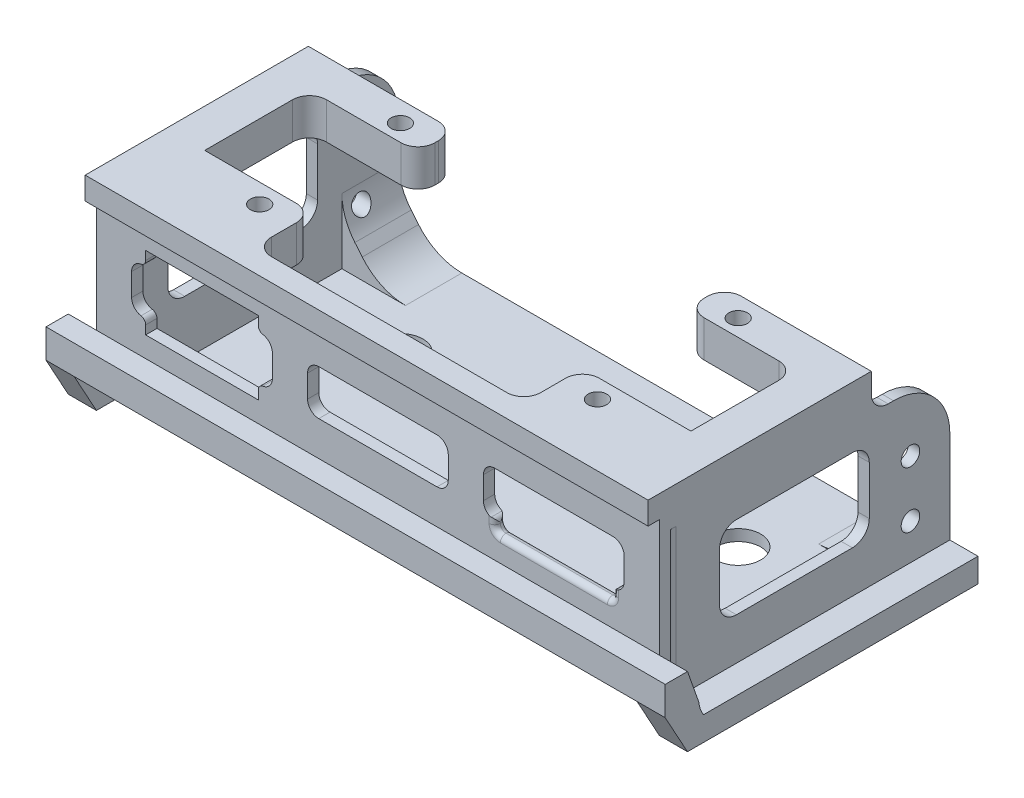
SolidWorks part; units mm, degrees
ref_plane "前视基准面" through (0, 0, 0) normal (0, 0, 1) x (1, 0, 0)
ref_plane "上视基准面" through (0, 0, 0) normal (0, 1, 0) x (1, 0, 0)
ref_plane "右视基准面" through (0, 0, 0) normal (1, 0, 0) x (0, 0, -1)
sketch "草图1" plane through (0, 0, 0) normal (0, 0, 1) x (1, 0, 0)
  line L1 (0, 0) -> (100, 0)
  line L2 (0, 0) -> (0, 30)
  line L3 (0, 30) -> (100, 30)
  line L4 (100, 0) -> (100, 30)
  dimension "D1" = 100
  dimension "D2" = 30
extrude "凸台-拉伸1" add sketch "草图1" along normal blind 2
sketch "草图2" plane through (0, 0, 2) normal (0, 0, 1) x (1, 0, 0)
  line L0 (0, 26) -> (100.6534, 26)
  line L4 (0, 30) -> (0, 0)
  line L5 (0, 0) -> (100, 0)
  line L6 (100, 0) -> (100, 30)
  line L7 (100, 30) -> (0, 30)
  line L8 (0, 30) -> (0, 0)
  line L9 (0, 0) -> (100, 0)
  line L10 (100, 0) -> (100, 30)
  line L11 (100, 30) -> (0, 30)
  line M6 (0, 30) -> (0, 0)
  line M8 (100, 0) -> (100, 30)
  line M9 (100, 30) -> (0, 30)
  dimension "D2" = 4
  dimension "D1" = 0
extrude "凸台-拉伸2" add sketch "草图2" along normal blind 2 contours L0 M6 M8 M9
sketch "草图3" plane through (0, 0, 2) normal (0, 0, 1) x (1, 0, 0)
  line L0 (37.5, 17.2904) -> (37.5, 13.2904)
  line L1 (8.25, 19.2904) -> (29.25, 19.2904)
  line L2 (6.25, 17.2904) -> (6.25, 13.2904)
  line L3 (8.25, 11.2904) -> (29.25, 11.2904)
  line L4 (100, 26) -> (0, 26)
  line L5 (0, 26) -> (0, 0)
  line L6 (0, 0) -> (100, 0)
  line L7 (100, 0) -> (100, 26)
  line L8 (100, 26) -> (0, 26)
  line L9 (0, 26) -> (0, 0)
  line L10 (0, 0) -> (100, 0)
  line L11 (100, 0) -> (100, 26)
  line L12 (31.25, 17.2904) -> (31.25, 13.2904)
  line L13 (39.5, 19.2904) -> (60.5, 19.2904)
  line L14 (62.5, 17.2904) -> (62.5, 13.2904)
  line L15 (39.5, 11.2904) -> (60.5, 11.2904)
  line L16 (68.75, 17.2904) -> (68.75, 13.2904)
  line L17 (70.75, 19.2904) -> (91.75, 19.2904)
  line L18 (93.75, 17.2904) -> (93.75, 13.2904)
  line L19 (70.75, 11.2904) -> (91.75, 11.2904)
  arc A0 (29.25, 19.2904) -> (31.25, 17.2904) centre (29.25, 17.2904) cw
  arc A1 (31.25, 13.2904) -> (29.25, 11.2904) centre (29.25, 13.2904) cw
  arc A2 (6.25, 13.2904) -> (8.25, 11.2904) centre (8.25, 13.2904) ccw
  arc A3 (6.25, 17.2904) -> (8.25, 19.2904) centre (8.25, 17.2904) cw
  arc A4 (37.5, 17.2904) -> (39.5, 19.2904) centre (39.5, 17.2904) cw
  arc A5 (37.5, 13.2904) -> (39.5, 11.2904) centre (39.5, 13.2904) ccw
  arc A6 (60.5, 19.2904) -> (62.5, 17.2904) centre (60.5, 17.2904) cw
  arc A7 (62.5, 13.2904) -> (60.5, 11.2904) centre (60.5, 13.2904) cw
  arc A8 (68.75, 17.2904) -> (70.75, 19.2904) centre (70.75, 17.2904) cw
  arc A9 (68.75, 13.2904) -> (70.75, 11.2904) centre (70.75, 13.2904) ccw
  arc A10 (91.75, 19.2904) -> (93.75, 17.2904) centre (91.75, 17.2904) cw
  arc A11 (93.75, 13.2904) -> (91.75, 11.2904) centre (91.75, 13.2904) cw
  dimension "D2" = 2
  dimension "D3" = 8
  dimension "D4" = 25
  dimension "D5" = 6.25
  dimension "D1" = 0
  dimension "D6" = 3
extrude "切除-拉伸1" cut sketch "草图3" against normal blind 2 contours L2 A2 L3 A1 L12 A0 L1 A3 | L0 A5 L15 A7 L14 A6 L13 A4 | L16 A9 L19 A11 L18 A10 L17 A8
sketch "草图4" plane through (100, 0, 0) normal (1, 0, 0) x (0, 0, -1)
  line L1 (-2, 0) -> (-5.9583, 0)
  line L2 (-2, 0) -> (-2, 5.1375)
  line L3 (-2, 5.1375) -> (-5.9583, 5.1375)
  line L4 (-5.9583, 0) -> (-5.9583, 5.1375)
  line L5 (5.0712, -5.2066) -> (49.6052, -5.2066)
  line L6 (0, 0) -> (0, 30)
  line L7 (0, 30) -> (-4, 30)
  line L8 (-4, 30) -> (-4, 26)
  line L9 (-4, 26) -> (-2, 26)
  line L10 (-2, 26) -> (-2, 0)
  line L11 (-2, 0) -> (0, 0)
  line L12 (0, 0) -> (0, 30)
  line L13 (0, 30) -> (-4, 30)
  line L14 (-4, 30) -> (-4, 26)
  line L15 (-4, 26) -> (-2, 26)
  line L16 (-2, 26) -> (-2, 0)
  line L17 (-2, 0) -> (0, 0)
  line L18 (5.0712, -5.2066) -> (5.0712, -7.2061)
  line L19 (5.0712, -7.2061) -> (49.6052, -7.2061)
  line L20 (49.6052, -5.2066) -> (49.6052, -7.2061)
  arc A0 (0, 0) -> (5.0712, -5.2066) centre (5.0693, -0.1355) ccw
  arc A1 (-2, 0) -> (5.0712, -7.2061) centre (5.0693, -0.1355) ccw
  line M11 (-2, 26) -> (-2, 0)
  line M12 (-2, 0) -> (0, 0)
  dimension "D1" = 0
extrude "凸台-拉伸3" add sketch "草图4" against normal blind 100 contours L4 L1 L3 M11 | A1 L18 A0 M12 | L20 L5 L18 L19
sketch "草图5" plane through (100, 0, 0) normal (1, 0, 0) x (0, 0, -1)
  line L0 (-2, 5.1375) -> (0, 5.1375)
  line L1 (-5.9583, 0) -> (-2.0013, -7.2061)
  line L2 (-2.0013, -7.2061) -> (17.8074, -7.2061)
  line L3 (-2, 5.1375) -> (0.8406, -2.9345)
  line L4 (0.8406, -2.9345) -> (49.6052, -2.9345)
  line L5 (49.6052, -2.9345) -> (49.6052, -7.2061)
  line L11 (0, 0) -> (0, 30)
  line L12 (0, 30) -> (-4, 30)
  line L13 (-4, 30) -> (-4, 26)
  line L14 (-4, 26) -> (-2, 26)
  line L15 (-2, 26) -> (-2, 5.1375)
  line L16 (-2, 5.1375) -> (-5.9583, 5.1375)
  line L17 (-5.9583, 5.1375) -> (-5.9583, 0)
  line L18 (-5.9583, 0) -> (-2, 0)
  line L19 (5.0712, -7.2061) -> (49.6052, -7.2061)
  line L20 (49.6052, -7.2061) -> (49.6052, -5.2066)
  line L21 (49.6052, -5.2066) -> (5.0712, -5.2066)
  line L22 (0, 0) -> (0, 30)
  line L23 (0, 30) -> (-4, 30)
  line L24 (-4, 30) -> (-4, 26)
  line L25 (-4, 26) -> (-2, 26)
  line L26 (-2, 26) -> (-2, 5.1375)
  line L27 (-2, 5.1375) -> (-5.9583, 5.1375)
  line L28 (-5.9583, 5.1375) -> (-5.9583, 0)
  line L29 (-5.9583, 0) -> (-2, 0)
  line L30 (5.0712, -7.2061) -> (49.6052, -7.2061)
  line L31 (49.6052, -7.2061) -> (49.6052, -5.2066)
  line L32 (49.6052, -5.2066) -> (5.0712, -5.2066)
  arc A2 (-2, 0) -> (5.0712, -7.2061) centre (5.0693, -0.1355) ccw
  arc A3 (0, 0) -> (5.0712, -5.2066) centre (5.0693, -0.1355) ccw
  arc A4 (-2, 0) -> (5.0712, -7.2061) centre (5.0693, -0.1355) ccw
  arc A5 (0, 0) -> (5.0712, -5.2066) centre (5.0693, -0.1355) ccw
  line M19 (-2, 5.1375) -> (-5.9583, 5.1375)
  line M20 (-5.9583, 5.1375) -> (-5.9583, 0)
  line M21 (-5.9583, 0) -> (-2, 0)
  arc M22 (-2, 0) -> (5.0712, -7.2061) centre (5.0693, -0.1355) ccw
  line M23 (5.0712, -7.2061) -> (49.6052, -7.2061)
  line M24 (49.6052, -7.2061) -> (49.6052, -5.2066)
  line M25 (49.6052, -5.2066) -> (5.0712, -5.2066)
  arc M26 (5.0712, -5.2066) -> (0, 0) centre (5.0693, -0.1355) cw
  dimension "D1" = 0
extrude "凸台-拉伸4" add sketch "草图5" along normal blind 5 contours L3 M19 M20 M21 M22 M23 M24 M25 M26 | L1 L2 M22 M21 | L5 L4 M26 M25
sketch "草图6" plane through (100, 0, 0) normal (1, 0, 0) x (0, 0, -1)
  line L0 (5.0712, -5.2066) -> (49.6052, -5.2066) construction
  line L1 (5.0712, -5.2066) -> (49.6052, -5.2066)
  line L3 (0, 23.4873) -> (49.6052, 23.4873)
  line L4 (0, 23.4873) -> (0, -5.2066)
  line L5 (0, -5.2066) -> (49.6052, -5.2066)
  line L6 (-2, 26) -> (-2, 5.1375)
  line L7 (-2, 5.1375) -> (0.0197, -0.6016)
  line L8 (0, 0) -> (0, 30)
  line L9 (0, 30) -> (-4, 30)
  line L10 (-4, 30) -> (-4, 26)
  line L11 (-4, 26) -> (-2, 26)
  line L12 (-2, 26) -> (-2, 5.1375)
  line L13 (-2, 5.1375) -> (0.0197, -0.6016)
  line L14 (0, 0) -> (0, 30)
  line L15 (0, 30) -> (-4, 30)
  line L16 (-4, 30) -> (-4, 26)
  line L17 (-4, 26) -> (-2, 26)
  line L18 (49.6052, 23.4873) -> (49.6052, -5.2066)
  arc A0 (0.8406, -2.9345) -> (5.0712, -5.2066) centre (5.0693, -0.1355) ccw construction
  arc A1 (0, 0) -> (0.0197, -0.6016) centre (5.0693, -0.1355) ccw
  arc A2 (0, 0) -> (0.0197, -0.6016) centre (5.0693, -0.1355) ccw
  arc A3 (0.8406, -2.9345) -> (5.0712, -5.2066) centre (5.0693, -0.1355) ccw
  arc A4 (0.0197, -0.6016) -> (0.8406, -2.9345) centre (5.0693, -0.1355) ccw construction
  arc A5 (0.0197, -0.6016) -> (0.8406, -2.9345) centre (5.0693, -0.1355) ccw
  arc M14 (0.0197, -0.6016) -> (0, 0) centre (5.0693, -0.1355) cw
  line M15 (0, 0) -> (0, 30)
  dimension "D1" = 0
extrude "凸台-拉伸5" add sketch "草图6" against normal blind 2 contours A5 A3 L1 L18 L3 L4 M14 M15
fillet "圆角1" radius 3 1 edges at (100, 15.5687, 2)
sketch "草图7" plane through (0, 30, 0) normal (0, 1, 0) x (1, 0, 0)
  line L0 (50, 0) -> (50, 26.3995) construction
  line L1 (100, 1) -> (100, 49.6052) construction
  line L2 (73.9207, 0) -> (100, 0)
  line L3 (73.9207, 0) -> (73.9207, 10.4199)
  line L4 (100, 0) -> (0, 0)
  line L5 (0, 0) -> (0, -4)
  line L6 (0, -4) -> (100, -4)
  line L7 (100, -4) -> (100, 0)
  line L8 (100, 0) -> (0, 0)
  line L9 (0, 0) -> (0, -4)
  line L10 (0, -4) -> (100, -4)
  line L11 (100, -4) -> (100, 0)
  line L12 (73.9207, 10.4199) -> (100, 10.4199)
  line L13 (100, 0) -> (100, 10.4199)
  line L14 (100, 1) -> (100, 49.6052)
  line L16 (73.9207, 29.0335) -> (100, 29.0335)
  line L17 (73.9207, 29.0335) -> (73.9207, 35.6447)
  line L18 (73.9207, 35.6447) -> (100, 35.6447)
  line L19 (100, 29.0335) -> (100, 35.6447)
  line L20 (93.1845, 29.0335) -> (100, 29.0335)
  line L21 (93.1845, 29.0335) -> (93.1845, 10.4199)
  line L22 (93.1845, 10.4199) -> (100, 10.4199)
  line L23 (100, 29.0335) -> (100, 10.4199)
  circle A0 centre (80, 7) radius 1.65
  circle A1 centre (80, 32) radius 1.65
  line M14 (100, 0) -> (0, 0)
  dimension "D2" = 3.3
  dimension "D5" = 2
  dimension "D3" = 30
  dimension "D4" = 7
  dimension "D1" = 0
extrude "凸台-拉伸7" add sketch "草图7" against normal up to surface (6.5127 mm away) contours L13 L12 L3 A0 M14 | L16 L21 L12 L14 | L18 L17 L16 L14 A1 up to face at (99.1742, 23.4873, -20.0406)
fillet "圆角2" radius 3 1 edges at (100, 28, 4)
fillet "圆角3" radius 3 7 edges at (73.9207, 26.7436, 0) (73.9207, 26.7436, -10.4199) (73.9207, 26.7436, -29.0335) (93.1845, 26.7436, -29.0335) (98, 11.7436, 0) (73.9207, 26.7436, -35.6447) (99, 23.4873, -35.6447)
sketch "草图8" plane through (0, 0, -49.6052) normal (0, 0, -1) x (-1, 0, 0)
  line L0 (-98, 2.7597) -> (-91.387, -5.2066)
  line L8 (0, -5.2066) -> (-98, -5.2066)
  line L9 (-98, -5.2066) -> (-98, 23.4873)
  line L10 (-98, 23.4873) -> (-100, 23.4873)
  line L11 (-100, 23.4873) -> (-100, -2.9345)
  line L12 (-100, -2.9345) -> (-105, -2.9345)
  line L13 (-105, -2.9345) -> (-105, -7.2061)
  line L14 (-105, -7.2061) -> (0, -7.2061)
  line L15 (0, -7.2061) -> (0, -5.2066)
  line L16 (0, -5.2066) -> (-98, -5.2066)
  line L17 (-98, -5.2066) -> (-98, 23.4873)
  line L18 (-98, 23.4873) -> (-100, 23.4873)
  line L19 (-100, 23.4873) -> (-100, -2.9345)
  line L20 (-100, -2.9345) -> (-105, -2.9345)
  line L21 (-105, -2.9345) -> (-105, -7.2061)
  line L22 (-105, -7.2061) -> (0, -7.2061)
  line L23 (0, -7.2061) -> (0, -5.2066)
  line M9 (0, -5.2066) -> (-98, -5.2066)
  line M10 (-98, -5.2066) -> (-98, 23.4873)
  dimension "D1" = 0
extrude "凸台-拉伸8" add sketch "草图8" against normal blind 10 contours L0 M10 M9
fillet "圆角4" radius 10 2 edges at (91.387, -5.2066, -44.6052) (98, 2.7597, -44.6052)
fillet "圆角5" radius 10 1 edges at (99, 23.4873, -49.6052)
sketch "草图9" plane through (98, 0, 0) normal (-1, 0, 0) x (0, 0, 1)
  line L9 (-38.6447, 23.4873) -> (-39.6052, 23.4873)
  line L10 (-49.6052, 13.4873) -> (-49.6052, 6.3694)
  line L11 (-49.6052, 6.3694) -> (-39.6052, 6.3694)
  line L12 (-39.6052, 6.3694) -> (-39.6052, -5.2066)
  line L13 (-39.6052, -5.2066) -> (-5.0712, -5.2066)
  line L14 (0, -0.271) -> (0, 0)
  line L15 (-3, 4.4942) -> (-3, 23.4873)
  line L16 (-3, 23.4873) -> (-35.6447, 23.4873)
  line L17 (-35.6447, 23.4873) -> (-35.6447, 26.4873)
  line L18 (-38.6447, 23.4873) -> (-39.6052, 23.4873)
  line L19 (-49.6052, 13.4873) -> (-49.6052, 6.3694)
  line L20 (-49.6052, 6.3694) -> (-39.6052, 6.3694)
  line L21 (-39.6052, 6.3694) -> (-39.6052, -5.2066)
  line L22 (-39.6052, -5.2066) -> (-5.0712, -5.2066)
  line L23 (0, -0.271) -> (0, 0)
  line L24 (-3, 4.4942) -> (-3, 23.4873)
  line L25 (-3, 23.4873) -> (-35.6447, 23.4873)
  line L26 (-35.6447, 23.4873) -> (-35.6447, 26.4873)
  circle A0 centre (-42.6052, 13.4873) radius 1.65
  circle A1 centre (-42.6052, 3.4873) radius 1.65
  arc A4 (-39.6052, 23.4873) -> (-49.6052, 13.4873) centre (-39.6052, 13.4873) ccw
  arc A5 (-5.0712, -5.2066) -> (0, -0.271) centre (-5.0693, -0.1355) ccw
  arc A6 (0, 0) -> (-3, 4.4942) centre (-5.0693, -0.1355) ccw
  arc A7 (-38.6447, 23.4873) -> (-35.6447, 26.4873) centre (-38.6447, 26.4873) ccw
  arc A8 (-39.6052, 23.4873) -> (-49.6052, 13.4873) centre (-39.6052, 13.4873) ccw
  arc A9 (-5.0712, -5.2066) -> (0, -0.271) centre (-5.0693, -0.1355) ccw
  arc A10 (0, 0) -> (-3, 4.4942) centre (-5.0693, -0.1355) ccw
  arc A11 (-38.6447, 23.4873) -> (-35.6447, 26.4873) centre (-38.6447, 26.4873) ccw
  dimension "D3" = 3.3
  dimension "D4" = 3.3
  dimension "D2" = 10
  dimension "D5" = 10
  dimension "D6" = 7
  dimension "D1" = 0
extrude "切除-拉伸2" cut sketch "草图9" against normal blind 3.3 and the other way blind 10 contours A0 | A1
ref_plane "基准面4" through (50, 0, 0) normal (1, 0, 0) x (0, 0, -1)
mirror "镜向1" about plane through (50, 0, 0) normal (1, 0, 0) of bodies 110
sketch "草图10" plane through (0, 23.4873, 0) normal (0, -1, 0) x (1, 0, 0)
  line L8 (73.9207, -3) -> (73.9207, -7.4199)
  line L9 (76.9207, -10.4199) -> (93.1845, -10.4199)
  line L10 (93.1845, -10.4199) -> (93.1845, -26.0335)
  line L11 (90.1845, -29.0335) -> (76.9207, -29.0335)
  line L12 (73.9207, -32.0335) -> (73.9207, -32.6447)
  line L13 (76.9207, -35.6447) -> (98, -35.6447)
  line L14 (98, -35.6447) -> (98, -3)
  line L15 (95, 0) -> (70.9207, 0)
  line L16 (73.9207, -3) -> (73.9207, -7.4199)
  line L17 (76.9207, -10.4199) -> (93.1845, -10.4199)
  line L18 (93.1845, -10.4199) -> (93.1845, -26.0335)
  line L19 (90.1845, -29.0335) -> (76.9207, -29.0335)
  line L20 (73.9207, -32.0335) -> (73.9207, -32.6447)
  line L21 (76.9207, -35.6447) -> (98, -35.6447)
  line L22 (98, -35.6447) -> (98, -3)
  line L23 (95, 0) -> (70.9207, 0)
  circle A0 centre (80, -32) radius 1.65 construction
  circle A1 centre (80, -32) radius 1.65
  circle A2 centre (80, -7) radius 1.65 construction
  circle A3 centre (80, -7) radius 1.65
  circle A4 centre (80, -32) radius 4
  circle A5 centre (80, -7) radius 4
  arc A6 (73.9207, -7.4199) -> (76.9207, -10.4199) centre (76.9207, -7.4199) ccw
  arc A7 (90.1845, -29.0335) -> (93.1845, -26.0335) centre (90.1845, -26.0335) ccw
  arc A8 (76.9207, -29.0335) -> (73.9207, -32.0335) centre (76.9207, -32.0335) ccw
  arc A9 (73.9207, -32.6447) -> (76.9207, -35.6447) centre (76.9207, -32.6447) ccw
  arc A10 (98, -3) -> (95, 0) centre (95, -3) ccw
  arc A11 (73.9207, -3) -> (70.9207, 0) centre (70.9207, -3) ccw
  arc A12 (73.9207, -7.4199) -> (76.9207, -10.4199) centre (76.9207, -7.4199) ccw
  arc A13 (90.1845, -29.0335) -> (93.1845, -26.0335) centre (90.1845, -26.0335) ccw
  arc A14 (76.9207, -29.0335) -> (73.9207, -32.0335) centre (76.9207, -32.0335) ccw
  arc A15 (73.9207, -32.6447) -> (76.9207, -35.6447) centre (76.9207, -32.6447) ccw
  arc A16 (98, -3) -> (95, 0) centre (95, -3) ccw
  arc A17 (73.9207, -3) -> (70.9207, 0) centre (70.9207, -3) ccw
  circle M15 centre (80, -7) radius 1.65
  circle M16 centre (80, -32) radius 1.65
  dimension "D2" = 8
  dimension "D3" = 8
  dimension "D1" = 0
extrude "切除-拉伸4" cut sketch "草图10" along normal blind 100 contours L17 A5 M15 | L17 A5 | L21 A4 L19 M16 | L19 A4 | L21 A4 | M16 | M15
sketch "草图11" plane through (100, 0, 0) normal (1, 0, 0) x (0, 0, -1)
  line L1 (11.6896, 19.1573) -> (32.2896, 19.1573)
  line L2 (8.6896, 16.1573) -> (8.6896, 7.5186)
  line L3 (11.6896, 4.5186) -> (32.2896, 4.5186)
  line L4 (35.2896, 16.1573) -> (35.2896, 7.5186)
  line L12 (35.6447, 26.4873) -> (35.6447, 30)
  line L13 (35.6447, 30) -> (-4, 30)
  line L14 (-4, 30) -> (-4, 26)
  line L15 (-4, 26) -> (-2, 26)
  line L16 (-2, 26) -> (-2, 5.1375)
  line L17 (-2, 5.1375) -> (0.0197, -0.6016)
  line L18 (0, 0) -> (0, 23.4873)
  line L19 (0, 23.4873) -> (1, 23.4873)
  line L20 (1, 23.4873) -> (1, -2.9345)
  line L21 (1, -2.9345) -> (49.6052, -2.9345)
  line L22 (49.6052, -2.9345) -> (49.6052, 13.4873)
  line L23 (39.6052, 23.4873) -> (38.6447, 23.4873)
  line L24 (35.6447, 26.4873) -> (35.6447, 30)
  line L25 (35.6447, 30) -> (-4, 30)
  line L26 (-4, 30) -> (-4, 26)
  line L27 (-4, 26) -> (-2, 26)
  line L28 (-2, 26) -> (-2, 5.1375)
  line L29 (-2, 5.1375) -> (0.0197, -0.6016)
  line L30 (0, 0) -> (0, 23.4873)
  line L31 (0, 23.4873) -> (1, 23.4873)
  line L32 (1, 23.4873) -> (1, -2.9345)
  line L33 (1, -2.9345) -> (49.6052, -2.9345)
  line L34 (49.6052, -2.9345) -> (49.6052, 13.4873)
  line L35 (39.6052, 23.4873) -> (38.6447, 23.4873)
  arc A0 (32.2896, 19.1573) -> (35.2896, 16.1573) centre (32.2896, 16.1573) cw
  arc A1 (35.2896, 7.5186) -> (32.2896, 4.5186) centre (32.2896, 7.5186) cw
  arc A2 (11.6896, 4.5186) -> (8.6896, 7.5186) centre (11.6896, 7.5186) cw
  arc A3 (0, 0) -> (0.0197, -0.6016) centre (5.0693, -0.1355) ccw
  arc A4 (49.6052, 13.4873) -> (39.6052, 23.4873) centre (39.6052, 13.4873) ccw
  arc A5 (35.6447, 26.4873) -> (38.6447, 23.4873) centre (38.6447, 26.4873) ccw
  arc A6 (0, 0) -> (0.0197, -0.6016) centre (5.0693, -0.1355) ccw
  arc A7 (49.6052, 13.4873) -> (39.6052, 23.4873) centre (39.6052, 13.4873) ccw
  arc A8 (35.6447, 26.4873) -> (38.6447, 23.4873) centre (38.6447, 26.4873) ccw
  arc A9 (8.6896, 16.1573) -> (11.6896, 19.1573) centre (11.6896, 16.1573) cw
  dimension "D3" = 3
  dimension "D2" = 26.6
  dimension "D1" = 0
extrude "切除-拉伸5" cut sketch "草图11" against normal blind 120
mirror "镜向2" about plane through (50, 0, 0) normal (1, 0, 0) of "切除-拉伸4"
sketch "草图12" plane through (0, 0, 2) normal (0, 0, 1) x (1, 0, 0)
  line L0 (8.25, 19.2904) -> (29.25, 19.2904) construction
  line L1 (8.25, 19.2904) -> (29.25, 19.2904)
  line L2 (8.25, 11.2904) -> (29.25, 11.2904) construction
  line L3 (8.25, 11.2904) -> (29.25, 11.2904)
  line L4 (0, 5.1375) -> (100, 5.1375)
  line L5 (100, 5.1375) -> (100, 26)
  line L6 (100, 26) -> (0, 26)
  line L7 (0, 26) -> (0, 5.1375)
  line L8 (0, 5.1375) -> (100, 5.1375)
  line L9 (100, 5.1375) -> (100, 26)
  line L10 (100, 26) -> (0, 26)
  line L11 (0, 26) -> (0, 5.1375)
  line L12 (6.25, 17.2904) -> (6.25, 13.2904) construction
  line L13 (8.75, 21.7904) -> (28.75, 21.7904)
  line L14 (8.75, 21.7904) -> (8.75, 8.7904)
  line L15 (8.75, 8.7904) -> (28.75, 8.7904)
  line L16 (28.75, 21.7904) -> (28.75, 8.7904)
  dimension "D2" = 8
  dimension "D3" = 20
  dimension "D4" = 13
  dimension "D5" = 2.5
  dimension "D6" = 2.5
  dimension "D1" = 0
extrude "切除-拉伸6" cut sketch "草图12" against normal blind 10 contours L16 L13 L14 L1 | L16 L3 L14 L15
fillet "圆角6" radius 1 4 edges at (28.75, 11.2904, 1) (28.75, 19.2904, 1) (8.75, 19.2904, 1) (8.75, 11.2904, 1)
sketch "草图13" plane through (0, 0, 2) normal (0, 0, 1) x (1, 0, 0)
  line L0 (70.75, 19.2904) -> (91.75, 19.2904) construction
  line L1 (70.75, 19.2904) -> (91.75, 19.2904)
  line L2 (70.75, 11.2904) -> (91.75, 11.2904) construction
  line L3 (70.75, 11.2904) -> (91.75, 11.2904)
  line L5 (70.75, 19.2904) -> (91.75, 19.2904)
  line L6 (70.75, 19.2904) -> (70.75, 9.2904)
  line L7 (70.75, 9.2904) -> (91.75, 9.2904)
  line L8 (91.75, 19.2904) -> (91.75, 9.2904)
  line M12 (91.75, 11.2904) -> (70.75, 11.2904)
  dimension "D1" = 2
extrude "切除-拉伸7" cut sketch "草图13" against normal blind 10 contours L8 L6 L7 M12
fillet "圆角7" radius 1 8 edges at (91.75, 10.2904, 0) (91.75, 10.2904, 2) (70.75, 10.2904, 2) (70.75, 10.2904, 0) (81.25, 9.2904, 2) (81.25, 9.2904, 0) (91.75, 11.2904, 1) (70.75, 11.2904, 1)
